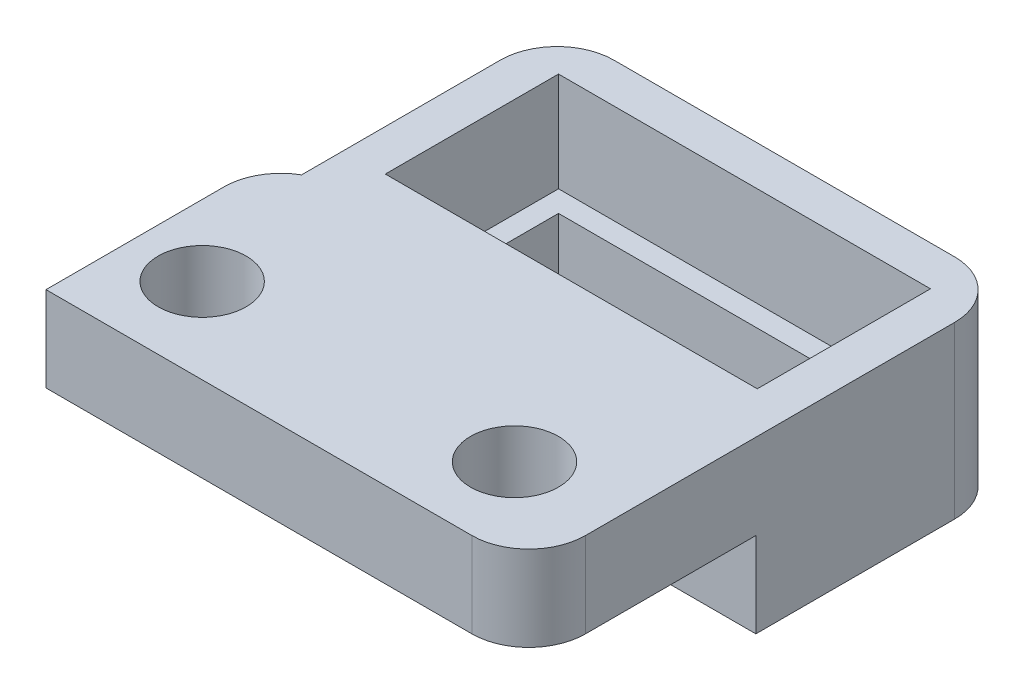
SolidWorks part; units mm, degrees
ref_plane "Alzado" through (0, 0, 0) normal (0, 0, 1) x (1, 0, 0)
ref_plane "Planta" through (0, 0, 0) normal (0, 1, 0) x (1, 0, 0)
ref_plane "Vista lateral" through (0, 0, 0) normal (1, 0, 0) x (0, 0, -1)
sketch "Croquis1" plane through (0, 0, 0) normal (0, 1, 0) x (1, 0, 0)
  line L0 (9, 18) -> (9, 0) construction
  line L1 (0, 0) -> (18, 0)
  line L2 (0, 0) -> (0, 18)
  line L3 (0, 18) -> (18, 18)
  line L4 (18, 0) -> (18, 18)
  circle A0 centre (3.5, 3) radius 1.55
  circle A1 centre (14.5, 3) radius 1.55
  dimension "D3" = 3.1
  dimension "D4" = 3
  dimension "D5" = 3.5
  dimension "D7" = 3
  dimension "D1" = 18
  dimension "D2" = 18
  dimension "D6" = 3.5
extrude "Saliente-Extruir1" add sketch "Croquis1" along normal blind 3
sketch "Croquis3" plane through (0, 3, 0) normal (0, 1, 0) x (1, 0, 0)
  line L0 (18, 0) -> (18, 18) construction
  line L1 (0, 18) -> (18, 18)
  line L2 (0, 18) -> (0, 8)
  line L3 (0, 8) -> (18, 8)
  line L4 (18, 18) -> (18, 8)
  dimension "D1" = 10
extrude "Saliente-Extruir3" add sketch "Croquis3" along normal blind 3
sketch "Croquis4" plane through (0, 0, 0) normal (0, -1, 0) x (1, 0, 0)
  line L1 (0, -18) -> (2, -18)
  line L2 (0, -18) -> (0, -8)
  line L3 (0, -8) -> (2, -8)
  line L4 (2, -18) -> (2, -8)
  dimension "D1" = 10
  dimension "D2" = 2
extrude "Cortar-Extruir1" cut sketch "Croquis4" against normal up to surface (6 mm away) up to face at (9, 6, -13)
sketch "Croquis7" plane through (0, 6, 0) normal (0, 1, 0) x (1, 0, 0)
  line L1 (3.45, 15.6) -> (16.55, 15.6)
  line L2 (3.45, 15.6) -> (3.45, 9.5)
  line L3 (3.45, 9.5) -> (16.55, 9.5)
  line L4 (16.55, 15.6) -> (16.55, 9.5)
  line L5 (2, 8) -> (18, 8) construction
  line L6 (2, 18) -> (2, 8) construction
  dimension "D1" = 6.1
  dimension "D2" = 13.1
  dimension "D3" = 1.5
  dimension "D4" = 1.45
extrude "Cortar-Extruir2" cut sketch "Croquis7" against normal up to surface (6 mm away) up to face at (6.6667, 0, -8.6667)
sketch "Croquis9" plane through (0, 0, 0) normal (0, -1, 0) x (1, 0, 0)
  line L0 (16.55, -15.6) -> (3.45, -15.6) construction
  line L1 (18, -18) -> (2, -18)
  line L2 (18, -18) -> (18, -8)
  line L3 (18, -8) -> (2, -8)
  line L4 (2, -18) -> (2, -8)
  line L5 (3.45, -15.6) -> (3.45, -9.5) construction
  line L6 (3.45, -9.5) -> (16.55, -9.5) construction
  line L7 (16.55, -9.5) -> (16.55, -15.6) construction
  line L8 (3.45, -9.5) -> (16.55, -9.5)
  line L9 (3.45, -15.6) -> (3.45, -9.5)
  line L10 (16.55, -15.6) -> (3.45, -15.6)
  line L11 (16.55, -9.5) -> (16.55, -15.6)
extrude "Saliente-Extruir4" add sketch "Croquis9" along normal blind 3
sketch "Croquis10" plane through (0, -3, 0) normal (0, -1, 0) x (1, 0, 0)
  line L0 (16.55, -15.6) -> (16.55, -9.5) construction
  line L1 (16.55, -9.5) -> (3.45, -9.5) construction
  line L2 (3.45, -9.5) -> (3.45, -15.6) construction
  line L3 (3.45, -15.6) -> (16.55, -15.6) construction
  line L4 (16.55, -15.6) -> (16.55, -9.5)
  line L5 (16.55, -9.5) -> (3.45, -9.5)
  line L6 (3.45, -9.5) -> (3.45, -15.6)
  line L7 (3.45, -15.6) -> (16.55, -15.6)
  line L8 (15.8, -14.85) -> (15.8, -10.25)
  line L9 (15.8, -10.25) -> (4.2, -10.25)
  line L10 (4.2, -10.25) -> (4.2, -14.85)
  line L11 (4.2, -14.85) -> (15.8, -14.85)
  dimension "D1" = 0.75
extrude "Saliente-Extruir6" add sketch "Croquis10" against normal blind 2.5
sketch "Croquis11" plane through (0, 6, 0) normal (0, 1, 0) x (1, 0, 0)
  line L0 (18, 8) -> (18, 18) construction
  line L1 (2, 18) -> (18, 18)
  line L2 (2, 18) -> (2, 17)
  line L3 (2, 17) -> (18, 17)
  line L4 (18, 18) -> (18, 17)
  dimension "D1" = 1
extrude "Cortar-Extruir4" cut sketch "Croquis11" against normal up to surface (9 mm away) up to face at (10, -3, -13)
fillet "Redondeo1" radius 2 3 edges at (18, 1.5, -17) (2, 1.5, -17) (18, 1.5, 0)
sketch "Croquis12" plane through (0, 0, 0) normal (-1, 0, 0) x (0, 0, 1)
  line L4 (0, 3) -> (-8, 3)
  line L5 (-8, 3) -> (-8, 0)
  line L6 (-8, 0) -> (0, 0)
  line L7 (0, 0) -> (0, 3)
  line L8 (0, 3) -> (-8, 3)
  line L9 (-8, 3) -> (-8, 0)
  line L10 (-8, 0) -> (0, 0)
  line L11 (0, 0) -> (0, 3)
  dimension "D1" = 0
extrude "Cortar-Extruir5" cut sketch "Croquis12" against normal blind 1
sketch "Croquis14" plane through (0, 0, -8) normal (0, 0, 1) x (1, 0, 0)
  line L4 (18, 6) -> (2, 6)
  line L5 (2, 6) -> (2, 3)
  line L6 (2, 3) -> (18, 3)
  line L7 (18, 3) -> (18, 6)
  line L8 (18, 6) -> (2, 6)
  line L9 (2, 6) -> (2, 3)
  line L10 (2, 3) -> (18, 3)
  line L11 (18, 3) -> (18, 6)
  dimension "D1" = 0
extrude "Cortar-Extruir6" cut sketch "Croquis14" against normal up to surface (9 mm away) up to face at (10, 1.5, -17)
fillet "Redondeo2" radius 2 1 edges at (1, 1.5, -8)
